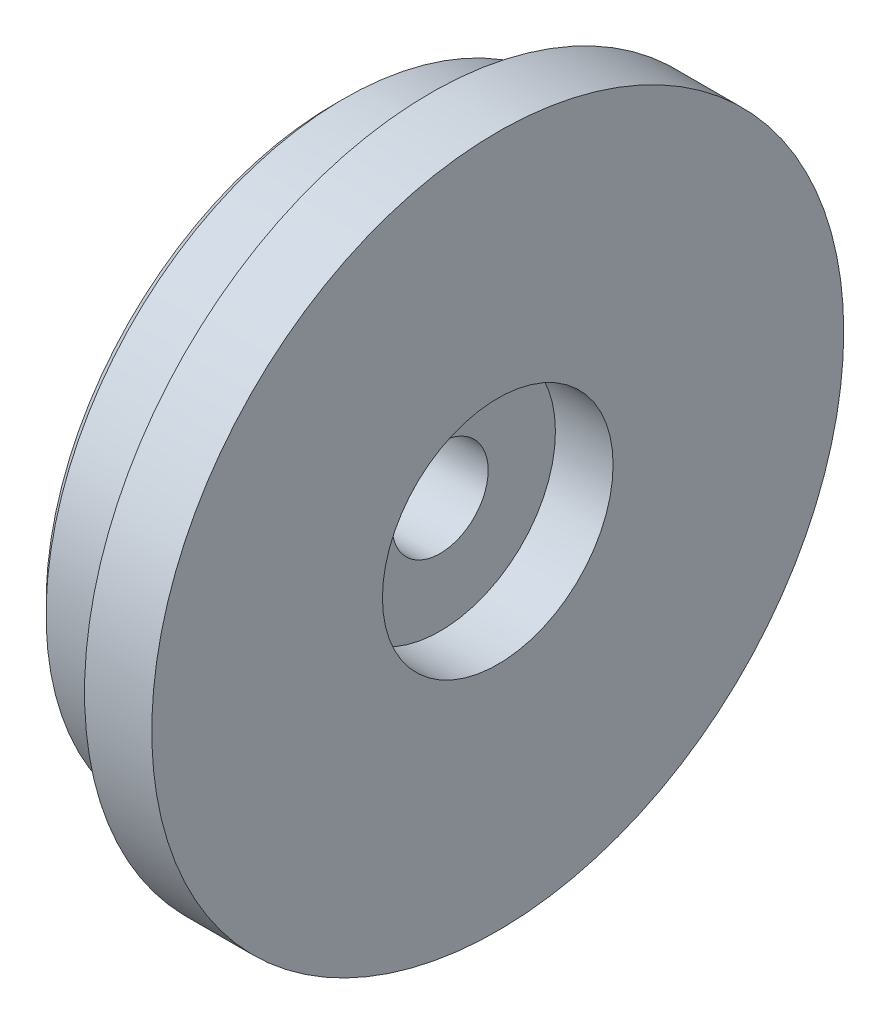
SolidWorks part; units mm, degrees
material "Alliage de zinc AC41A, brut"
ref_plane "Plan de face" through (0, 0, 0) normal (0, 0, 1) x (1, 0, 0)
ref_plane "Plan de dessus" through (0, 0, 0) normal (0, 1, 0) x (1, 0, 0)
ref_plane "Plan de droite" through (0, 0, 0) normal (1, 0, 0) x (0, 0, -1)
sketch "Esquisse1" plane through (0, 0, 0) normal (0, 0, 1) x (1, 0, 0)
  line L1 (0, 18) -> (-3.5, 18)
  line L2 (0, 18) -> (0, 6)
  line L3 (-3.5, 18) -> (-3.5, 15)
  line L4 (-3.5, 15) -> (-4.5, 15)
  line L5 (-4.5, 15) -> (-4.5, 15.5)
  line L6 (-4.5, 15.5) -> (-8, 15.5)
  line L8 (0, 6) -> (-3, 6)
  line L9 (-3, 6) -> (-3, 2.5)
  line L10 (-3, 2.5) -> (-8.5, 2.5)
  line L11 (-8, 15.5) -> (-8.5, 15)
  line L12 (-8.5, 2.5) -> (-8.5, 5)
  line L13 (-8.5, 5) -> (-5.75, 5)
  line L14 (-5, 5.75) -> (-5, 11.25)
  line L15 (-5.75, 12) -> (-8.5, 12)
  line L16 (-8.5, 12) -> (-8.5, 15)
  line L17 (-5, 11.25) -> (-5.75, 12)
  line L18 (-5.75, 5) -> (-5, 5.75)
  line L19 (0, 0) -> (-8.5, 0) construction
  line L20 (0, 0) -> (0, 6) construction
  point P13 (-5, 5)
  point P15 (-5, 12)
  dimension "D2" = 3.5
  dimension "D3" = 12
  dimension "D4" = 3
  dimension "D5" = 1
  dimension "D6" = 0.5
  dimension "D7" = 2.75
  dimension "D8" = 2.5
  dimension "D9" = 3
  dimension "D10" = 3.5
  dimension "D11" = 5.5
  dimension "D12" = 3.5
  dimension "D19" = 18
  dimension "D13" = 0.5
  dimension "D14" = 7
  dimension "D15" = 3
  dimension "D17" = 0.75
  dimension "D20" = 0.75
  dimension "D18" = 0.75
  dimension "D16" = 3.5
  dimension "D21" = 0.75
  dimension "D22" = 6
revolve "Révolution1789" add sketch "Esquisse1" angle 360 about L19
cosmetic thread "Représentation de filetage1" parameters "D2"=30
cosmetic thread "Représentation de filetage2" parameters "D2"=6
cosmetic thread "Cosmetic Thread1" parameters "D1"=5, "D2"=6
